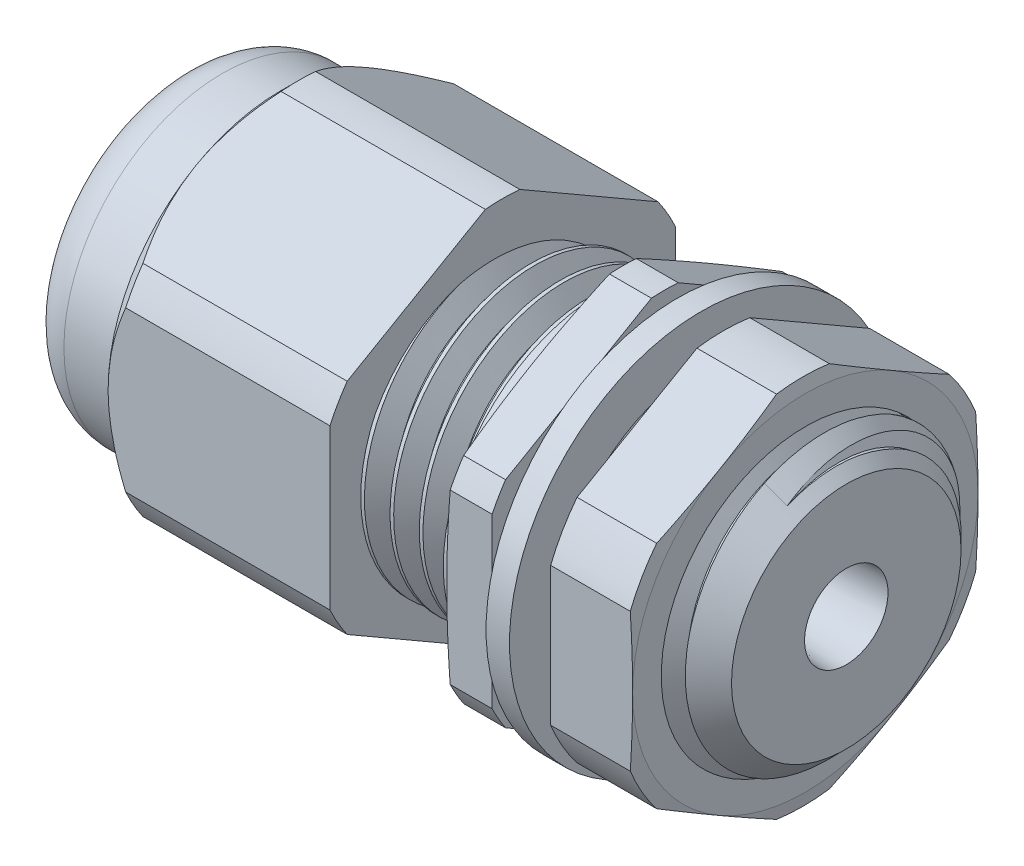
SolidWorks part; units mm, degrees
note: '?' marks a value the reader was unsure of.
ref_plane "Front Plane" through (0, 0, 0) normal (0, 0, 1) x (1, 0, 0)
ref_plane "Top Plane" through (0, 0, 0) normal (0, 1, 0) x (1, 0, 0)
ref_plane "Right Plane" through (0, 0, 0) normal (1, 0, 0) x (0, 0, -1)
sketch "Sketch33" plane through (0, 0, 0) normal (0, 0, 1) x (1, 0, 0)
  line L0 (0, 0) -> (-36.6524, 0) construction
ref_axis "Axis1" through (0, 0, 0) along (-1, 0, 0)?
sketch "Sketch10" plane through (0, 0, 0) normal (0, 0, 1) x (1, 0, 0)
  line L0 (114.3469, 0) -> (-132.0634, 0) construction
  line L1 (-15.1666, 1.016) -> (-24.5364, 1.016)
  line L2 (0, 1.8108) -> (0, 6.25)
  line L3 (-7.874, 6.25) -> (0, 6.25)
  line L4 (-7.874, 28.956) -> (-7.874, 6.25)
  line L5 (-7.874, 28.956) -> (-9.8425, 28.956)
  line L6 (-9.8425, 28.956) -> (-9.8425, 6.25)
  line L7 (-15.1666, 6.25) -> (-9.8425, 6.25)
  line L8 (-15.1666, 6.25) -> (-15.1666, 28.956)
  line L9 (-15.1666, 28.956) -> (-24.5364, 28.956)
  line L10 (-24.5364, 28.956) -> (-24.5364, 6.8715)
  line L11 (-24.5364, 6.8715) -> (-28.956, 6.8715)
  line L12 (-28.956, 6.8715) -> (-28.956, 1.4224)
  line L13 (-28.956, 1.4224) -> (-24.5364, 1.4224)
  line L14 (-24.5364, 1.4224) -> (-24.5364, 1.016)
  line L15 (-15.1666, 1.016) -> (0, 1.8108)
  line L16 (-28.956, 1.4224) -> (-28.956, 0) construction
  line L17 (-28.956, 0) -> (0, 0) construction
  line L18 (-28.956, 0) -> (-28.956, 28.956) construction
  line L19 (-28.956, 28.956) -> (-24.5364, 28.956) construction
  line L20 (-15.1666, 6.25) -> (0, 6.25) construction
  line L21 (0, 6.25) -> (0, -6.25) construction
  line L22 (114.3469, 7.493) -> (114.3469, -7.493) construction
  line L23 (-8.8582, 7.493) -> (-8.8582, -7.493) construction
  point P27 (-8.8583, 28.956)
  point P28 (-8.8582, 0)
  dimension "D2" = 1.9685
  dimension "ID" = 2.032
  dimension "D3" = 0
  dimension "D4" = 2.8448
  dimension "D7" = 3
  dimension "D9" = 4.4196
  dimension "D10" = 9.3698
  dimension "Thread Length" = 7.874
  dimension "Body Length" = 21.082
  dimension "NPT" = 12.5
  dimension "Dome" = 13.743
  dimension "Hex" = 14.986
  dimension "F1 Hex" = 14.986
revolve "Revolve2" add sketch "Sketch10" angle 360 about L0
chamfer "Chamfer2" distance 1.27 angle 45 1 edges at (0, 0, -6.25)
sketch "Sketch12" plane through (-24.5364, 0, 0) normal (-1, 0, 0) x (0, 0, 1)
  line L0 (6.7437, 4.7587) -> (7.493, 3.4609) construction
  line L1 (-0.7493, 8.2196) -> (-6.7437, 4.7587)
  line L2 (-7.493, 3.4609) -> (-7.493, -3.4609)
  line L3 (-6.7437, -4.7587) -> (-0.7493, -8.2196)
  line L4 (0.7493, -8.2196) -> (6.7437, -4.7587)
  line L5 (7.493, -3.4609) -> (7.493, 3.4609)
  line L6 (6.7437, 4.7587) -> (0.7493, 8.2196)
  circle A0 centre (0, 0) radius 7.493 construction
  arc A1 (0.7493, 8.2196) -> (-0.7493, 8.2196) centre (0, 0) ccw
  arc A2 (-6.7437, 4.7587) -> (-7.493, 3.4609) centre (0, 0) ccw
  arc A3 (-7.493, -3.4609) -> (-6.7437, -4.7587) centre (0, 0) ccw
  arc A4 (-0.7493, -8.2196) -> (0.7493, -8.2196) centre (0, 0) ccw
  arc A5 (6.7437, -4.7587) -> (7.493, -3.4609) centre (0, 0) ccw
  arc A6 (7.493, 3.4609) -> (6.7437, 4.7587) centre (0, 0) ccw
  dimension "D2" = 14.986
  dimension "D1" = 1.4986
extrude "Cut-Extrude2" cut sketch "Sketch12" against normal up to surface (9.3698 mm away) flip side to cut up to face at (-15.1666, 0, -28.956)
sketch "Sketch34" plane through (-9.8425, 0, 0) normal (-1, 0, 0) x (0, 0, 1)
  line L0 (6.9115, 4.6618) -> (7.493, 3.6546) construction
  line L1 (-0.5815, 8.3164) -> (-6.9115, 4.6618)
  line L2 (-7.493, 3.6546) -> (-7.493, -3.6546)
  line L3 (-6.9115, -4.6618) -> (-0.5815, -8.3164)
  line L4 (0.5815, -8.3164) -> (6.9115, -4.6618)
  line L5 (7.493, -3.6546) -> (7.493, 3.6546)
  line L6 (6.9115, 4.6618) -> (0.5815, 8.3164)
  line L7 (0, 8.3367) -> (0, 0) construction
  line L8 (0, -8.3367) -> (0, 0) construction
  line L10 (-0.5815, 8.3164) -> (0.5815, -8.3164) construction
  line L11 (-6.9115, 4.6618) -> (6.9115, -4.6618) construction
  line L12 (-7.2198, 4.1684) -> (0, 0) construction
  circle A0 centre (0, 0) radius 7.493 construction
  arc A1 (0.5815, 8.3164) -> (-0.5815, 8.3164) centre (0, 0) ccw
  arc A2 (-6.9115, 4.6618) -> (-7.493, 3.6546) centre (0, 0) ccw
  arc A3 (-7.493, -3.6546) -> (-6.9115, -4.6618) centre (0, 0) ccw
  arc A4 (-0.5815, -8.3164) -> (0.5815, -8.3164) centre (0, 0) ccw
  arc A5 (6.9115, -4.6618) -> (7.493, -3.6546) centre (0, 0) ccw
  arc A6 (7.493, 3.6546) -> (6.9115, 4.6618) centre (0, 0) ccw
  dimension "D1" = 4
  dimension "D2" = 14.986
  dimension "D3" = 4
extrude "Cut-Extrude8" cut sketch "Sketch34" against normal through all flip side to cut
ref_plane "Plane1" through (-5.334, 0, 0) normal (1, 0, 0) x (0, 0, -1)
sketch "Sketch27" plane through (-5.334, 0, 0) normal (1, 0, 0) x (0, 0, -1)
  line L0 (0, 8.6522) -> (0, 8.0726) construction
  line L1 (0, 8.6522) -> (-7.493, 4.3261) construction
  line L2 (-7.493, 4.3261) -> (-7.493, -4.3261) construction
  line L3 (-7.493, -4.3261) -> (0, -8.6522) construction
  line L4 (0, -8.6522) -> (7.493, -4.3261) construction
  line L5 (7.493, -4.3261) -> (7.493, 4.3261) construction
  line L6 (7.493, 4.3261) -> (0, 8.6522) construction
  line L7 (0, 8.0726) -> (0, 7.493) construction
  line L9 (-1.1453, 7.9909) -> (-6.3477, 4.9873)
  line L10 (-7.493, 3.0036) -> (-7.493, -3.0036)
  line L11 (-6.3477, -4.9873) -> (-1.1453, -7.9909)
  line L12 (1.1453, -7.9909) -> (6.3477, -4.9873)
  line L13 (7.493, -3.0036) -> (7.493, 3.0036)
  line L14 (6.3477, 4.9873) -> (1.1453, 7.9909)
  circle A0 centre (0, 0) radius 6.25 construction
  circle A1 centre (0, 0) radius 6.25 construction
  circle A2 centre (0, 0) radius 7.493 construction
  circle A3 centre (0, 0) radius 8.0726 construction
  arc A4 (-6.3477, 4.9873) -> (-7.493, 3.0036) centre (0, 0) ccw
  arc A5 (1.1453, 7.9909) -> (-1.1453, 7.9909) centre (0, 0) ccw
  arc A6 (7.493, 3.0036) -> (6.3477, 4.9873) centre (0, 0) ccw
  arc A7 (6.3477, -4.9873) -> (7.493, -3.0036) centre (0, 0) ccw
  arc A8 (-1.1453, -7.9909) -> (1.1453, -7.9909) centre (0, 0) ccw
  arc A9 (-7.493, -3.0036) -> (-6.3477, -4.9873) centre (0, 0) ccw
  circle A10 centre (0, 0) radius 7.493 construction
  circle A11 centre (0, 0) radius 6.25 construction
  circle A12 centre (0, 0) radius 6.25
  dimension "D1" = 14.986
extrude "Boss-Extrude3" add sketch "Sketch27" along normal blind 3.556 separate body
fillet "Fillet4" radius 1.8796 1 edges at (-28.956, 0, -6.8715)
sketch "Sketch19" plane through (-24.5364, 0, 0) normal (-1, 0, 0) x (0, 0, 1)
  line L0 (7.493, -3.4609) -> (7.493, 3.4609) construction
  circle A0 centre (0, 0) radius 7.493
extrude "Cut-Extrude3" cut sketch "Sketch19" against normal blind 2 draft 45 flip side to cut
sketch "Sketch20" plane through (0, 0, 0) normal (0, 0, 1) x (1, 0, 0)
  line L0 (-25.0444, 1.4224) -> (-25.0444, 1.016)
  line L1 (-15.1666, 1.016) -> (-24.5364, 1.016) construction
  line L3 (-24.5364, 1.4224) -> (-28.956, 1.4224) construction
  line L4 (-25.0444, 1.016) -> (-28.194, 1.016)
  line L5 (-28.194, 1.016) -> (-28.194, 1.1684)
  line L6 (-24.5364, 1.4224) -> (-24.5364, 1.016) construction
  line L10 (0, 0) -> (-38.0535, 0) construction
  line L11 (-27.94, 1.4224) -> (-25.0444, 1.4224)
  line L12 (-28.956, 4.9919) -> (-28.956, -4.9919) construction
  arc A0 (-27.94, 1.4224) -> (-28.194, 1.1684) centre (-27.94, 1.1684) ccw
  point P14 (-28.194, 1.4224)
  dimension "D1" = 0.762
  dimension "D2" = 0.254
  dimension "D3" = 0.508
revolve "Revolve3" add sketch "Sketch20" angle 360 about L10
sketch "Sketch24" plane through (-15.1666, 0, 0) normal (1, 0, 0) x (0, 0, -1)
  line L6 (6.7437, 4.7587) -> (0.7493, 8.2196)
  line L7 (-0.7493, 8.2196) -> (-6.7437, 4.7587)
  line L8 (-7.493, 3.4609) -> (-7.493, -3.4609)
  line L9 (-6.7437, -4.7587) -> (-0.7493, -8.2196)
  line L10 (0.7493, -8.2196) -> (6.7437, -4.7587)
  line L11 (7.493, -3.4609) -> (7.493, 3.4609)
  line L12 (6.7437, 4.7587) -> (0.7493, 8.2196)
  line L13 (-0.7493, 8.2196) -> (-6.7437, 4.7587)
  line L14 (-7.493, 3.4609) -> (-7.493, -3.4609)
  line L15 (-6.7437, -4.7587) -> (-0.7493, -8.2196)
  line L16 (0.7493, -8.2196) -> (6.7437, -4.7587)
  line L17 (7.493, -3.4609) -> (7.493, 3.4609)
  circle A2 centre (0, 0) radius 4.98 construction
  circle A3 centre (0, 0) radius 4.98
  arc A6 (0.7493, 8.2196) -> (-0.7493, 8.2196) centre (0, 0) ccw
  arc A7 (-6.7437, 4.7587) -> (-7.493, 3.4609) centre (0, 0) ccw
  arc A8 (-7.493, -3.4609) -> (-6.7437, -4.7587) centre (0, 0) ccw
  arc A9 (-0.7493, -8.2196) -> (0.7493, -8.2196) centre (0, 0) ccw
  arc A10 (6.7437, -4.7587) -> (7.493, -3.4609) centre (0, 0) ccw
  arc A11 (7.493, 3.4609) -> (6.7437, 4.7587) centre (0, 0) ccw
  arc A12 (0.7493, 8.2196) -> (-0.7493, 8.2196) centre (0, 0) ccw
  arc A13 (-6.7437, 4.7587) -> (-7.493, 3.4609) centre (0, 0) ccw
  arc A14 (-7.493, -3.4609) -> (-6.7437, -4.7587) centre (0, 0) ccw
  arc A15 (-0.7493, -8.2196) -> (0.7493, -8.2196) centre (0, 0) ccw
  arc A16 (6.7437, -4.7587) -> (7.493, -3.4609) centre (0, 0) ccw
  arc A17 (7.493, 3.4609) -> (6.7437, 4.7587) centre (0, 0) ccw
  dimension "D1" = 0
sketch "Sketch25" plane through (-15.1666, 0, 0) normal (1, 0, 0) x (0, 0, -1)
  circle A0 centre (0, 0) radius 6.25 construction
  circle A1 centre (0, 0) radius 6.25
curve "Helix/Spiral1" pitch 1.27 height 25.4 turns 20 parameters "Pitch"=1.27
sketch "Sketch26" plane through (0, 0, 0) normal (0, 0, 1) x (1, 0, 0)
  line L2 (-15.687, 6.2492) -> (-15.687, 6.3866) construction
  line L3 (-15.052, 6.3866) -> (-16.2823, 6.3179) construction
  line L4 (-16.322, 6.3866) -> (-15.0917, 6.3179)
  line L5 (-15.1313, 6.2492) -> (-16.2426, 6.2492) construction
  line L6 (-16.322, 6.3866) -> (-16.2823, 6.3179)
  line L7 (-15.052, 6.3866) -> (-15.0917, 6.3179) construction
  line L8 (-15.687, 5.2868) -> (-15.687, 5.4243) construction
  line L9 (-15.052, 6.3866) -> (-16.322, 6.3866) construction
  line L10 (-15.0917, 6.3179) -> (-16.2823, 6.3179) construction
  line L11 (-15.687, 5.2868) -> (-16.2426, 6.2492) construction
  line L12 (-15.1313, 6.2492) -> (-15.687, 5.2868) construction
  line L13 (-15.687, 5.4243) -> (-15.687, 5.5617) construction
  line L14 (-15.6076, 5.4243) -> (-15.1313, 6.2492)
  line L15 (-15.7663, 5.4243) -> (-16.2426, 6.2492)
  line L16 (-15.6076, 5.4243) -> (-15.7663, 5.4243)
  line L17 (-16.2426, 6.2492) -> (-16.2823, 6.3179)
  line L18 (-15.687, 5.5617) -> (-15.687, 5.6992) construction
  line L19 (-15.687, 5.6992) -> (-15.687, 5.8367) construction
  line L20 (-15.687, 5.8367) -> (-15.687, 5.9742) construction
  line L21 (-15.687, 5.9742) -> (-15.687, 6.1117) construction
  line L22 (-15.687, 6.1117) -> (-15.687, 6.2492) construction
  line L23 (-15.1313, 6.2492) -> (-15.0917, 6.3179)
  point P1 (-15.687, 6.3179)
  dimension "D1" = 1.27
  dimension "D2" = 0.1588
sweep "Cut-Sweep1" cut profiles "Sketch26" path "Helix/Spiral1"
extrude "Boss-Extrude1" add sketch "Sketch24" against normal up to vertex (8.6091 mm away) and the other way blind 0.254 up to point (-23.7757, 4.7587, -6.7437)
sketch "Sketch29" plane through (-1.778, 0, 0) normal (1, 0, 0) x (0, 0, -1)
  line L0 (-1.1453, 7.9909) -> (-6.3477, 4.9873) construction
  circle A0 centre (0, 0) radius 7.493
extrude "Cut-Extrude5" cut sketch "Sketch29" against normal blind 5.08 draft 80 flip side to cut
sketch "Sketch30" plane through (-9.8425, 0, 0) normal (1, 0, 0) x (0, 0, -1)
  line L1 (-6.9115, 4.6618) -> (-0.5815, 8.3164) construction
  circle A0 centre (0, 0) radius 7.493
extrude "Cut-Extrude7" cut sketch "Sketch30" along normal blind 5.08 draft 80 flip side to cut
sketch "Sketch32" plane through (0, 0, 0) normal (0, 0, 1) x (1, 0, 0)
  line L0 (-6.2984, 8.3164) -> (-6.2984, 6.2754)
  line L1 (-6.2984, 8.3164) -> (-7.3144, 8.3164)
  line L2 (-6.2984, 6.2754) -> (-7.3144, 6.2754)
  line L3 (-7.3144, 8.3164) -> (-7.3144, 6.2754)
  line L4 (-6.2984, 8.3164) -> (-7.3144, 6.2754) construction
  line L5 (-6.2984, 6.2754) -> (-7.3144, 8.3164) construction
  line L6 (-7.874, 28.956) -> (-7.874, 6.25) construction
  line L7 (-7.874, 8.3164) -> (-9.6937, 8.3164) construction
  point P1 (-6.8064, 7.2959)
  dimension "D1" = 0.5596
  dimension "D2" = 0.0254
  dimension "D3" = 1.016
revolve "Revolve4" add sketch "Sketch32" angle 360 about L0
sketch "Sketch35" plane through (-7.874, 0, 0) normal (1, 0, 0) x (0, 0, -1)
  circle A0 centre (0, 0) radius 6.25 construction
  circle A1 centre (0, 0) radius 1.016
  circle A2 centre (0, 0) radius 6.858
  dimension "D1" = 2.032
  dimension "D2" = 12.5
  dimension "D3" = 13.716
extrude "Boss-Extrude4" add sketch "Sketch35" against normal blind 2.7559
fillet "Fillet5" radius 0.1968 1 edges at (-9.8425, 0, 6.858)
equation "\"D10@Sketch10\" = \"Body Length@Sketch10\"/2.25"
equation "\"D2@Sketch10\" = \"Thread Length@Sketch10\"/4"
equation "\"D4@Sketch10\" = \"ID@Sketch10\"*1.4"
equation "\"D1@Sketch12\" = \"Hex@Sketch10\"/10"
equation "\"D1@Sketch26\" = \"Pitch@helix/spiral1\""
equation "\"D2@Sketch12\" = \"Hex@sketch10\""
equation "\"Dome@Sketch10\" = (\"Hex@Sketch10\"+\"NPT@Sketch10\")/2"
equation "\"D1@Sketch27\" = \"Hex@sketch10\""
equation "\"D2@Sketch34\" = \"F1 Hex@Sketch10\""
equation "\"D1@Sketch35\" = \"ID@Sketch10\""
equation "\"D2@Sketch35\" = \"NPT@Sketch10\""
equation "\"D1@Boss-Extrude4\" = \"D2@Sketch10\"*1.4"
equation "\"D1@Fillet5\"=\"D2@Sketch10\"*.1"
